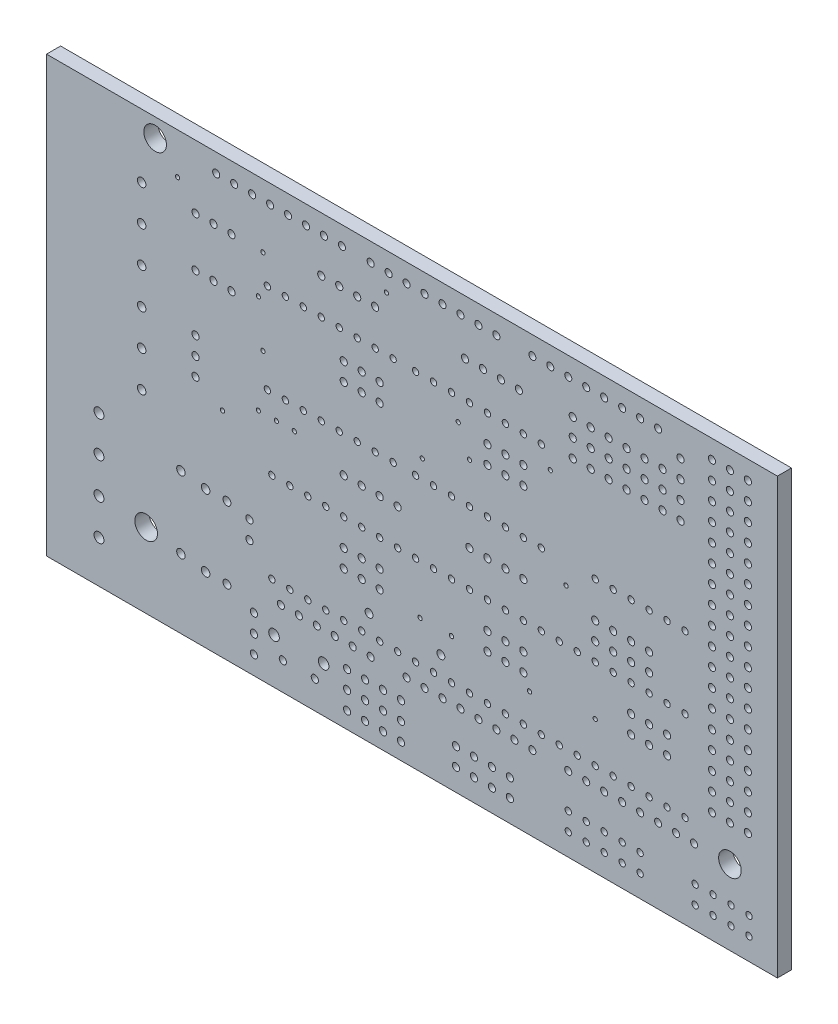
SolidWorks part; units mm, degrees
ref_plane "Front Plane" through (0, 0, 0) normal (0, 0, 1) x (1, 0, 0)
ref_plane "Top Plane" through (0, 0, 0) normal (0, 1, 0) x (1, 0, 0)
ref_plane "Right Plane" through (0, 0, 0) normal (1, 0, 0) x (0, 0, -1)
ref_plane "Plane1" through (0, 0, 0) normal (0, 0, -1) x (-1, 0, 0)
sketch "Sketch1" plane through (-1.6696, 0, 0) normal (0, 0, -1) x (-1, 0, 0)
  line L0 (-99.6292, -73.2069) -> (32.156, -73.2069)
  line L1 (32.156, -73.2069) -> (32.156, 21.3177)
  line L2 (32.156, 21.3177) -> (-99.6292, 21.3177)
  line L3 (-99.6292, 21.3177) -> (-99.6292, -73.2069)
  circle A0 centre (-14.6383, -51.3454) radius 0.5105
  circle A1 centre (-14.0002, -37.6006) radius 0.5105
  circle A2 centre (-14.0002, -40.153) radius 0.5105
  circle A3 centre (-43.353, -50.8412) radius 0.5105
  circle A4 centre (-45.9055, -50.8412) radius 0.5105
  circle A5 centre (-48.4579, -50.8412) radius 0.5105
  circle A6 centre (-51.0103, -50.8412) radius 0.5105
  circle A7 centre (-41.2084, -40.6622) radius 0.5615
  circle A8 centre (-30.9987, -40.6622) radius 0.5615
  circle A9 centre (-10.8097, -47.1722) radius 0.5615
  circle A10 centre (-10.8097, -36.9625) radius 0.5615
  circle A11 centre (-24.2098, -2.5048) radius 0.5105
  circle A12 centre (-26.7622, -2.5048) radius 0.5105
  circle A13 centre (-29.3146, -2.5048) radius 0.5105
  circle A14 centre (-31.867, -2.5048) radius 0.5105
  circle A15 centre (-44.6292, -2.5048) radius 0.5105
  circle A16 centre (-47.1817, -2.5048) radius 0.5105
  circle A17 centre (-49.7341, -2.5048) radius 0.5105
  circle A18 centre (-52.2865, -2.5048) radius 0.5105
  circle A19 centre (-7.7787, -36.9625) radius 0.6029
  circle A20 centre (-7.7787, -47.1722) radius 0.6029
  circle A21 centre (-4.2691, -46.6937) radius 0.6029
  circle A22 centre (-4.2691, -36.484) radius 0.6029
  circle A23 centre (-75.2583, -7.1311) radius 0.5105
  circle A24 centre (-75.2583, -4.5786) radius 0.5105
  circle A25 centre (-75.2583, -2.0262) radius 0.5105
  circle A26 centre (-75.2583, 0.5262) radius 0.5105
  circle A27 centre (-27.4004, -13.9907) radius 0.5105
  circle A28 centre (-27.4004, -11.4383) radius 0.5105
  circle A29 centre (-29.9528, -13.9907) radius 0.5105
  circle A30 centre (-29.9528, -11.4383) radius 0.5105
  circle A31 centre (-32.5053, -13.9907) radius 0.5105
  circle A32 centre (-32.5053, -11.4383) radius 0.5105
  circle A33 centre (-47.8198, -13.9907) radius 0.5105
  circle A34 centre (-47.8198, -11.4383) radius 0.5105
  circle A35 centre (-50.3722, -13.9907) radius 0.5105
  circle A36 centre (-50.3722, -11.4383) radius 0.5105
  circle A37 centre (-52.9246, -13.9907) radius 0.5105
  circle A38 centre (-52.9246, -11.4383) radius 0.5105
  circle A39 centre (-27.4004, -36.9625) radius 0.5105
  circle A40 centre (-27.4004, -34.4101) radius 0.5105
  circle A41 centre (-29.9528, -36.9625) radius 0.5105
  circle A42 centre (-29.9528, -34.4101) radius 0.5105
  circle A43 centre (-32.5053, -36.9625) radius 0.5105
  circle A44 centre (-32.5053, -34.4101) radius 0.5105
  circle A45 centre (-47.8198, -36.9625) radius 0.5105
  circle A46 centre (-47.8198, -34.4101) radius 0.5105
  circle A47 centre (-50.3722, -36.9625) radius 0.5105
  circle A48 centre (-50.3722, -34.4101) radius 0.5105
  circle A49 centre (-52.9246, -36.9625) radius 0.5105
  circle A50 centre (-52.9246, -34.4101) radius 0.5105
  circle A51 centre (-68.2391, -36.9625) radius 0.5105
  circle A52 centre (-68.2391, -34.4101) radius 0.5105
  circle A53 centre (-70.7916, -36.9625) radius 0.5105
  circle A54 centre (-70.7916, -34.4101) radius 0.5105
  circle A55 centre (-73.344, -36.9625) radius 0.5105
  circle A56 centre (-73.344, -34.4101) radius 0.5105
  circle A57 centre (-63.1343, -20.3718) radius 0.4522
  circle A58 centre (-65.6867, -20.3718) radius 0.4522
  circle A59 centre (-68.2391, -20.3718) radius 0.4522
  circle A60 centre (-70.7916, -20.3718) radius 0.4522
  circle A61 centre (-73.344, -20.3718) radius 0.4522
  circle A62 centre (-75.8964, -20.3718) radius 0.4522
  circle A63 centre (-14.6383, -53.8978) radius 0.5105
  circle A64 centre (-8.8953, -3.7811) radius 0.5105
  circle A65 centre (-11.4477, -3.7811) radius 0.5105
  circle A66 centre (-6.3428, -3.7811) radius 0.5105
  circle A67 centre (-8.8953, -10.8003) radius 0.5105
  circle A68 centre (-11.4477, -10.8003) radius 0.5105
  circle A69 centre (-6.3428, -10.8003) radius 0.5105
  circle A70 centre (-6.343, -21.3289) radius 0.5105
  circle A71 centre (-6.343, -23.8814) radius 0.5105
  circle A72 centre (-6.343, -18.7765) radius 0.5105
  circle A73 centre (-18.7477, -52.5706) radius 0.5105
  circle A74 centre (-23.291, -52.5706) radius 0.5105
  circle A75 centre (-17.497, -50.0692) radius 0.753
  circle A76 centre (-24.5417, -50.0692) radius 0.753
  circle A77 centre (-27.8789, -54.1914) radius 0.5105
  circle A78 centre (-27.8789, -51.639) radius 0.5105
  circle A79 centre (-27.8789, -49.0866) radius 0.5105
  circle A80 centre (-30.4315, -54.1913) radius 0.5105
  circle A81 centre (-30.4315, -51.6389) radius 0.5105
  circle A82 centre (-30.4315, -49.0865) radius 0.5105
  circle A83 centre (-32.9838, -54.1913) radius 0.5105
  circle A84 centre (-32.9838, -51.6389) radius 0.5105
  circle A85 centre (-32.9838, -49.0865) radius 0.5105
  circle A86 centre (-35.5363, -54.1913) radius 0.5105
  circle A87 centre (-35.5363, -51.6389) radius 0.5105
  circle A88 centre (-35.5363, -49.0865) radius 0.5105
  circle A89 centre (-43.353, -53.3938) radius 0.5105
  circle A90 centre (-45.9055, -53.3938) radius 0.5105
  circle A91 centre (-48.4579, -53.3938) radius 0.5105
  circle A92 centre (-51.0103, -53.3938) radius 0.5105
  circle A93 centre (1.3143, -29.3053) radius 0.6029
  circle A94 centre (1.3143, -24.2004) radius 0.6029
  circle A95 centre (1.3143, -19.0956) radius 0.6029
  circle A96 centre (1.3143, -13.9907) radius 0.6029
  circle A97 centre (1.3143, -8.8859) radius 0.6029
  circle A98 centre (1.3143, -3.7811) radius 0.6029
  circle A99 centre (-84.9893, -50.8412) radius 0.4522
  circle A100 centre (-84.9893, -53.3937) radius 0.4522
  circle A101 centre (-82.4369, -50.8412) radius 0.4522
  circle A102 centre (-82.4369, -53.3937) radius 0.4522
  circle A103 centre (-79.8845, -50.8412) radius 0.4522
  circle A104 centre (-79.8845, -53.3937) radius 0.4522
  circle A105 centre (-77.3321, -50.8412) radius 0.4522
  circle A106 centre (-77.3321, -53.3937) radius 0.4522
  circle A107 centre (-26.7623, -7.6097) radius 0.4522
  circle A108 centre (-29.3147, -7.6097) radius 0.4522
  circle A109 centre (-24.2099, -7.6097) radius 0.4522
  circle A110 centre (-21.6575, -7.6097) radius 0.4522
  circle A111 centre (-34.4196, -20.3718) radius 0.4522
  circle A112 centre (-16.5526, -20.3718) radius 0.4522
  circle A113 centre (-34.4196, -7.6097) radius 0.4522
  circle A114 centre (-19.105, -7.6097) radius 0.4522
  circle A115 centre (-19.105, -20.3718) radius 0.4522
  circle A116 centre (-21.6575, -20.3718) radius 0.4522
  circle A117 centre (-24.2099, -20.3718) radius 0.4522
  circle A118 centre (-26.7623, -20.3718) radius 0.4522
  circle A119 centre (-29.3147, -20.3718) radius 0.4522
  circle A120 centre (-31.8671, -20.3718) radius 0.4522
  circle A121 centre (-31.8671, -7.6097) radius 0.4522
  circle A122 centre (-16.5526, -7.6097) radius 0.4522
  circle A123 centre (-47.8198, -7.6097) radius 0.4522
  circle A124 centre (-50.3722, -7.6097) radius 0.4522
  circle A125 centre (-45.2674, -7.6097) radius 0.4522
  circle A126 centre (-42.7149, -7.6097) radius 0.4522
  circle A127 centre (-55.477, -20.3718) radius 0.4522
  circle A128 centre (-37.6101, -20.3718) radius 0.4522
  circle A129 centre (-55.477, -7.6097) radius 0.4522
  circle A130 centre (-40.1625, -7.6097) radius 0.4522
  circle A131 centre (-40.1625, -20.3718) radius 0.4522
  circle A132 centre (-42.7149, -20.3718) radius 0.4522
  circle A133 centre (-45.2674, -20.3718) radius 0.4522
  circle A134 centre (-47.8198, -20.3718) radius 0.4522
  circle A135 centre (-50.3722, -20.3718) radius 0.4522
  circle A136 centre (-52.9246, -20.3718) radius 0.4522
  circle A137 centre (-52.9246, -7.6097) radius 0.4522
  circle A138 centre (-37.6101, -7.6097) radius 0.4522
  circle A139 centre (-27.4005, -30.5815) radius 0.4522
  circle A140 centre (-29.9529, -30.5815) radius 0.4522
  circle A141 centre (-24.8481, -30.5815) radius 0.4522
  circle A142 centre (-22.2957, -30.5815) radius 0.4522
  circle A143 centre (-35.0578, -43.3436) radius 0.4522
  circle A144 centre (-17.1908, -43.3436) radius 0.4522
  circle A145 centre (-35.0578, -30.5815) radius 0.4522
  circle A146 centre (-19.7433, -30.5815) radius 0.4522
  circle A147 centre (-19.7433, -43.3436) radius 0.4522
  circle A148 centre (-22.2957, -43.3436) radius 0.4522
  circle A149 centre (-24.8481, -43.3436) radius 0.4522
  circle A150 centre (-27.4005, -43.3436) radius 0.4522
  circle A151 centre (-29.9529, -43.3436) radius 0.4522
  circle A152 centre (-32.5054, -43.3436) radius 0.4522
  circle A153 centre (-32.5054, -30.5815) radius 0.4522
  circle A154 centre (-17.1908, -30.5815) radius 0.4522
  circle A155 centre (-47.8198, -30.5815) radius 0.4522
  circle A156 centre (-50.3722, -30.5815) radius 0.4522
  circle A157 centre (-45.2674, -30.5815) radius 0.4522
  circle A158 centre (-42.7149, -30.5815) radius 0.4522
  circle A159 centre (-55.477, -43.3436) radius 0.4522
  circle A160 centre (-37.6101, -43.3436) radius 0.4522
  circle A161 centre (-55.477, -30.5815) radius 0.4522
  circle A162 centre (-40.1625, -30.5815) radius 0.4522
  circle A163 centre (-40.1625, -43.3436) radius 0.4522
  circle A164 centre (-42.7149, -43.3436) radius 0.4522
  circle A165 centre (-45.2674, -43.3436) radius 0.4522
  circle A166 centre (-47.8198, -43.3436) radius 0.4522
  circle A167 centre (-50.3722, -43.3436) radius 0.4522
  circle A168 centre (-52.9246, -43.3436) radius 0.4522
  circle A169 centre (-52.9246, -30.5815) radius 0.4522
  circle A170 centre (-37.6101, -30.5815) radius 0.4522
  circle A171 centre (-68.2391, -30.5815) radius 0.4522
  circle A172 centre (-70.7916, -30.5815) radius 0.4522
  circle A173 centre (-65.6867, -30.5815) radius 0.4522
  circle A174 centre (-63.1343, -30.5815) radius 0.4522
  circle A175 centre (-75.8964, -43.3436) radius 0.4522
  circle A176 centre (-58.0295, -43.3436) radius 0.4522
  circle A177 centre (-75.8964, -30.5815) radius 0.4522
  circle A178 centre (-60.5819, -30.5815) radius 0.4522
  circle A179 centre (-60.5819, -43.3436) radius 0.4522
  circle A180 centre (-63.1343, -43.3436) radius 0.4522
  circle A181 centre (-65.6867, -43.3436) radius 0.4522
  circle A182 centre (-68.2391, -43.3436) radius 0.4522
  circle A183 centre (-70.7916, -43.3436) radius 0.4522
  circle A184 centre (-73.344, -43.3436) radius 0.4522
  circle A185 centre (-73.344, -30.5815) radius 0.4522
  circle A186 centre (-58.0295, -30.5815) radius 0.4522
  circle A187 centre (-84.8299, -40.7911) radius 0.5105
  circle A188 centre (-84.8299, -38.2387) radius 0.5105
  circle A189 centre (-84.8299, -35.6863) radius 0.5105
  circle A190 centre (-84.8299, -33.1339) radius 0.5105
  circle A191 centre (-84.8299, -30.5815) radius 0.5105
  circle A192 centre (-84.8299, -28.029) radius 0.5105
  circle A193 centre (-84.8299, -25.4766) radius 0.5105
  circle A194 centre (-84.8299, -22.9242) radius 0.5105
  circle A195 centre (-84.8299, -20.3718) radius 0.5105
  circle A196 centre (-84.8299, -17.8194) radius 0.5105
  circle A197 centre (-84.8299, -15.2669) radius 0.5105
  circle A198 centre (-84.8299, -12.7145) radius 0.5105
  circle A199 centre (-84.8299, -10.1621) radius 0.5105
  circle A200 centre (-84.8299, -7.6097) radius 0.5105
  circle A201 centre (-84.8299, -5.0573) radius 0.5105
  circle A202 centre (-84.8299, -2.5048) radius 0.5105
  circle A203 centre (-84.8299, 0.0476) radius 0.5105
  circle A204 centre (-84.8299, 2.6) radius 0.5105
  circle A205 centre (-59.3057, -53.3937) radius 0.4522
  circle A206 centre (-59.3057, -50.8412) radius 0.4522
  circle A207 centre (-61.8581, -53.3937) radius 0.4522
  circle A208 centre (-61.8581, -50.8412) radius 0.4522
  circle A209 centre (-64.4105, -53.3937) radius 0.4522
  circle A210 centre (-64.4105, -50.8412) radius 0.4522
  circle A211 centre (-66.9629, -53.3937) radius 0.4522
  circle A212 centre (-66.9629, -50.8412) radius 0.4522
  circle A213 centre (-69.5153, -53.3937) radius 0.4522
  circle A214 centre (-69.5153, -50.8412) radius 0.4522
  circle A215 centre (-82.2774, -45.896) radius 1.6078
  circle A216 centre (0.6762, -45.896) radius 1.6078
  circle A217 centre (-0.6, 2.6) radius 1.6078
  circle A218 centre (-21.0194, -45.896) radius 0.5024
  circle A219 centre (-23.5718, -45.896) radius 0.5024
  circle A220 centre (-79.725, 2.6) radius 0.5024
  circle A221 centre (-82.2774, 2.6) radius 0.5024
  circle A222 centre (-36.3339, -45.896) radius 0.5024
  circle A223 centre (-38.8863, -45.896) radius 0.5024
  circle A224 centre (-41.4387, -45.896) radius 0.5024
  circle A225 centre (-43.9911, -45.896) radius 0.5024
  circle A226 centre (-46.5436, -45.896) radius 0.5024
  circle A227 centre (-49.096, -45.896) radius 0.5024
  circle A228 centre (-51.6484, -45.896) radius 0.5024
  circle A229 centre (-54.2008, -45.896) radius 0.5024
  circle A230 centre (-59.3057, -45.896) radius 0.5024
  circle A231 centre (-61.8581, -45.896) radius 0.5024
  circle A232 centre (-64.4105, -45.896) radius 0.5024
  circle A233 centre (-66.9629, -45.896) radius 0.5024
  circle A234 centre (-69.5153, -45.896) radius 0.5024
  circle A235 centre (-72.0678, -45.896) radius 0.5024
  circle A236 centre (-74.6202, -45.896) radius 0.5024
  circle A237 centre (-77.1726, -45.896) radius 0.5024
  circle A238 centre (-9.2782, 2.6) radius 0.5024
  circle A239 centre (-43.9911, 2.6) radius 0.5024
  circle A240 centre (-41.4387, 2.6) radius 0.5024
  circle A241 centre (-38.8863, 2.6) radius 0.5024
  circle A242 centre (-36.3339, 2.6) radius 0.5024
  circle A243 centre (-33.7815, 2.6) radius 0.5024
  circle A244 centre (-31.229, 2.6) radius 0.5024
  circle A245 centre (-27.1452, 2.6) radius 0.5024
  circle A246 centre (-24.5927, 2.6) radius 0.5024
  circle A247 centre (-22.0403, 2.6) radius 0.5024
  circle A248 centre (-19.4879, 2.6) radius 0.5024
  circle A249 centre (-16.9355, 2.6) radius 0.5024
  circle A250 centre (-14.3831, 2.6) radius 0.5024
  circle A251 centre (-54.2008, 2.6) radius 0.5024
  circle A252 centre (-56.7532, 2.6) radius 0.5024
  circle A253 centre (-59.3057, 2.6) radius 0.5024
  circle A254 centre (-61.8581, 2.6) radius 0.5024
  circle A255 centre (-64.4105, 2.6) radius 0.5024
  circle A256 centre (-66.9629, 2.6) radius 0.5024
  circle A257 centre (-69.5153, 2.6) radius 0.5024
  circle A258 centre (-72.0678, 2.6) radius 0.5024
  circle A259 centre (-79.725, 0.0476) radius 0.5024
  circle A260 centre (-82.2774, 0.0476) radius 0.5024
  circle A261 centre (-79.725, -2.5048) radius 0.5024
  circle A262 centre (-82.2774, -2.5048) radius 0.5024
  circle A263 centre (-79.725, -5.0573) radius 0.5024
  circle A264 centre (-82.2774, -5.0573) radius 0.5024
  circle A265 centre (-79.725, -7.6097) radius 0.5024
  circle A266 centre (-82.2774, -7.6097) radius 0.5024
  circle A267 centre (-79.725, -10.1621) radius 0.5024
  circle A268 centre (-82.2774, -10.1621) radius 0.5024
  circle A269 centre (-79.725, -12.7145) radius 0.5024
  circle A270 centre (-82.2774, -12.7145) radius 0.5024
  circle A271 centre (-79.725, -15.2669) radius 0.5024
  circle A272 centre (-82.2774, -15.2669) radius 0.5024
  circle A273 centre (-79.725, -17.8194) radius 0.5024
  circle A274 centre (-82.2774, -17.8194) radius 0.5024
  circle A275 centre (-79.725, -20.3718) radius 0.5024
  circle A276 centre (-82.2774, -20.3718) radius 0.5024
  circle A277 centre (-79.725, -22.9242) radius 0.5024
  circle A278 centre (-82.2774, -22.9242) radius 0.5024
  circle A279 centre (-79.725, -25.4766) radius 0.5024
  circle A280 centre (-82.2774, -25.4766) radius 0.5024
  circle A281 centre (-79.725, -28.029) radius 0.5024
  circle A282 centre (-82.2774, -28.029) radius 0.5024
  circle A283 centre (-79.725, -30.5815) radius 0.5024
  circle A284 centre (-82.2774, -30.5815) radius 0.5024
  circle A285 centre (-79.725, -33.1339) radius 0.5024
  circle A286 centre (-82.2774, -33.1339) radius 0.5024
  circle A287 centre (-79.725, -35.6863) radius 0.5024
  circle A288 centre (-82.2774, -35.6863) radius 0.5024
  circle A289 centre (-79.725, -38.2387) radius 0.5024
  circle A290 centre (-82.2774, -38.2387) radius 0.5024
  circle A291 centre (-26.1242, -45.896) radius 0.5024
  circle A292 centre (-28.6766, -45.896) radius 0.5024
  circle A293 centre (-11.8306, 2.6) radius 0.5024
  circle A294 centre (-79.725, -40.7911) radius 0.5024
  circle A295 centre (-82.2774, -40.7911) radius 0.5024
  circle A296 centre (-18.4669, -45.896) radius 0.5024
  circle A297 centre (-49.096, 2.6) radius 0.5024
  circle A298 centre (-46.5436, 2.6) radius 0.5024
  circle A299 centre (-31.229, -45.896) radius 0.5024
  circle A300 centre (-14.6383, -48.7675) radius 0.5105
  circle A301 centre (-62.4962, -2.0263) radius 0.5105
  circle A302 centre (-62.4962, -4.5787) radius 0.5105
  circle A303 centre (-62.4962, -7.1312) radius 0.5105
  circle A304 centre (-59.9438, -2.0263) radius 0.5105
  circle A305 centre (-59.9438, -4.5787) radius 0.5105
  circle A306 centre (-59.9438, -7.1312) radius 0.5105
  circle A307 centre (-27.4004, -25.4768) radius 0.5105
  circle A308 centre (-29.9528, -25.4768) radius 0.5105
  circle A309 centre (-32.5053, -25.4768) radius 0.5105
  circle A310 centre (-35.0577, -25.4768) radius 0.5105
  circle A311 centre (7.3763, -35.2077) radius 0.7019
  circle A312 centre (7.3763, -40.3125) radius 0.7019
  circle A313 centre (7.3763, -45.4174) radius 0.7019
  circle A314 centre (7.3763, -50.5222) radius 0.7019
  circle A315 centre (-67.601, -2.0263) radius 0.5105
  circle A316 centre (-67.601, -4.5787) radius 0.5105
  circle A317 centre (-67.601, -7.1312) radius 0.5105
  circle A318 centre (-65.0486, -2.0263) radius 0.5105
  circle A319 centre (-65.0486, -4.5787) radius 0.5105
  circle A320 centre (-65.0486, -7.1312) radius 0.5105
  circle A321 centre (-45.2674, -25.4767) radius 0.5105
  circle A322 centre (-47.8198, -25.4767) radius 0.5105
  circle A323 centre (-50.3722, -25.4767) radius 0.5105
  circle A324 centre (-52.9246, -25.4767) radius 0.5105
  circle A325 centre (-72.7059, -2.0263) radius 0.5105
  circle A326 centre (-72.7059, -4.5787) radius 0.5105
  circle A327 centre (-72.7059, -7.1312) radius 0.5105
  circle A328 centre (-70.1534, -2.0263) radius 0.5105
  circle A329 centre (-70.1534, -4.5787) radius 0.5105
  circle A330 centre (-70.1534, -7.1312) radius 0.5105
  circle A331 centre (-63.1343, -25.4766) radius 0.5105
  circle A332 centre (-65.6867, -25.4766) radius 0.5105
  circle A333 centre (-68.2391, -25.4766) radius 0.5105
  circle A334 centre (-70.7916, -25.4766) radius 0.5105
  circle A335 centre (-63.1343, -28.029) radius 0.5105
  circle A336 centre (-65.6867, -28.029) radius 0.5105
  circle A337 centre (-68.2391, -28.029) radius 0.5105
  circle A338 centre (-70.7916, -28.029) radius 0.5105
  circle A339 centre (-38.2482, -37.6006) radius 0.3015
  circle A340 centre (-15.2764, -23.5623) radius 0.3015
  circle A341 centre (-20.3813, -23.5623) radius 0.3015
  circle A342 centre (-17.8288, -23.5623) radius 0.3015
  circle A343 centre (-15.2764, -9.524) radius 0.3015
  circle A344 centre (-10.1716, -26.1147) radius 0.3015
  circle A345 centre (-38.5672, -17.8194) radius 0.3015
  circle A346 centre (-15.9145, -3.7811) radius 0.3015
  circle A347 centre (-3.7905, -0.5905) radius 0.3015
  circle A348 centre (-53.7924, -38.8768) radius 0.3015
  circle A349 centre (-63.1343, -37.6006) radius 0.3015
  circle A350 centre (-42.7149, -37.6006) radius 0.3015
  circle A351 centre (-43.6721, -10.8002) radius 0.3015
  circle A352 centre (-33.4624, 0.0476) radius 0.3015
  circle A353 centre (-15.9145, -15.905) radius 0.3015
  circle A354 centre (-45.2674, -14.6288) radius 0.3015
  circle A355 centre (-58.9866, -23.2433) radius 0.3015
  circle A356 centre (-56.7532, -10.1621) radius 0.3015
extrude "Boss-Extrude1" add sketch "Sketch1" against normal blind 2
sketch "Sketch4" plane through (-1.6696, 0, 2) normal (0, 0, 1) x (1, 0, 0)
  line L1 (-14.8309, 5.2363) -> (89.0239, 5.2363)
  line L2 (-14.8309, 5.2363) -> (-14.8309, -56.5287)
  line L3 (-14.8309, -56.5287) -> (89.0239, -56.5287)
  line L4 (89.0239, 5.2363) -> (89.0239, -56.5287)
  line L5 (-33.6375, 26.1042) -> (102.425, 26.1042)
  line L6 (-33.6375, 26.1042) -> (-33.6375, -76.7559)
  line L7 (-33.6375, -76.7559) -> (102.425, -76.7559)
  line L8 (102.425, 26.1042) -> (102.425, -76.7559)
extrude "Cut-Extrude1" cut sketch "Sketch4" against normal blind 10
